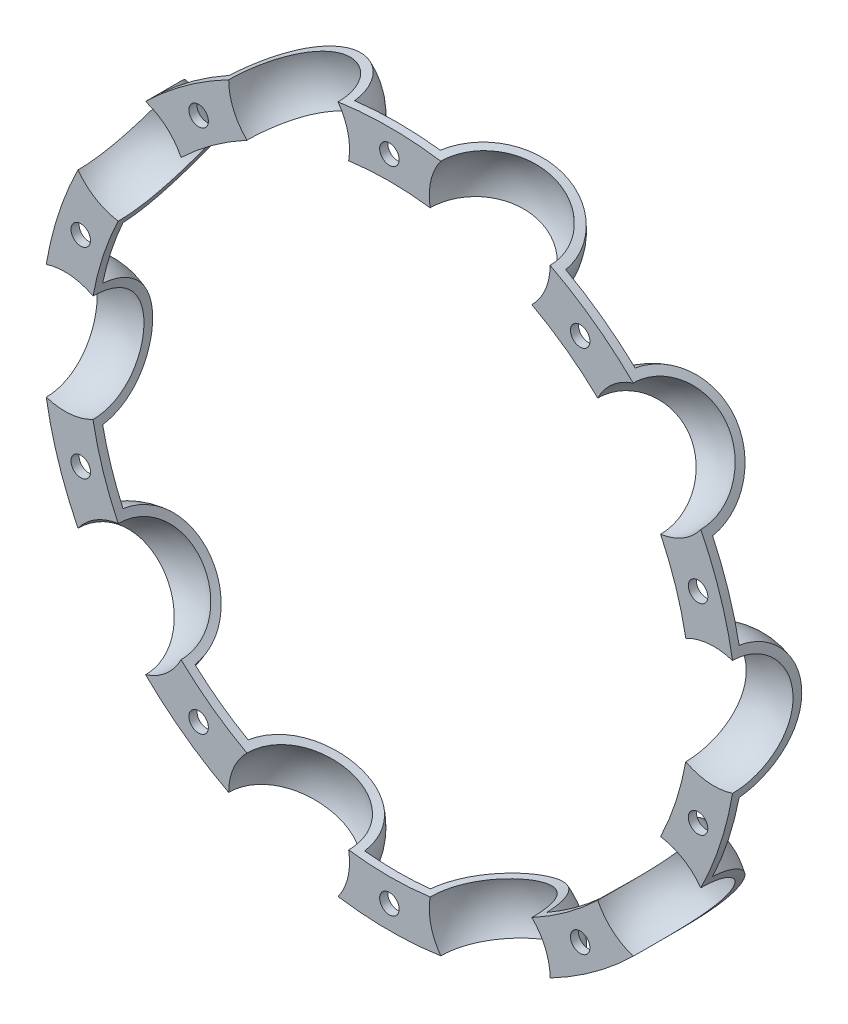
SolidWorks part; units mm, degrees
ref_plane "Front Plane" through (0, 0, 0) normal (0, 0, 1) x (1, 0, 0)
ref_plane "Top Plane" through (0, 0, 0) normal (0, 1, 0) x (1, 0, 0)
ref_plane "Right Plane" through (0, 0, 0) normal (1, 0, 0) x (0, 0, -1)
sketch "Sketch1" plane through (0, 0, 0) normal (0, 0, 1) x (1, 0, 0)
  circle A0 centre (0, 0) radius 10.71
  circle A1 centre (0, 0) radius 9.27
  dimension "D1" = 21.42
  dimension "D2" = 18.54
extrude "Boss-Extrude1" add sketch "Sketch1" along normal mid plane 2.11
sketch "Sketch2" plane through (0, 0, 1.055) normal (0, 0, 1) x (1, 0, 0)
  line L0 (8.13, 0) -> (11.85, 0) construction
  line L1 (8.13, 0) -> (11.85, 0)
  line L2 (9.27, 0) -> (10.71, 0) construction
  arc A0 (11.85, 0) -> (8.13, 0) centre (9.99, 0) ccw
  circle A1 centre (0, 0) radius 9.27 construction
  circle A2 centre (0, 0) radius 10.71 construction
  point P12 (9.99, 0)
  dimension "D1" = 3.72
revolve "Cut-Revolve1" cut sketch "Sketch2" angle 360 about L0
pattern_circular "CirPattern1" count 10 over 360 about axis through (0, 0, 0) along (0, 0, 1) of "Cut-Revolve1"
shell "Shell2" thickness 0.25
sketch "Sketch3" plane through (0, 0, 0.805) normal (0, 0, -1) x (-1, 0, 0)
  line L0 (0, 10.71) -> (0, 9.27) construction
  arc A0 (1.321, 10.6282) -> (-1.321, 10.6282) centre (0, 0) ccw construction
  arc A1 (1.0116, 9.2146) -> (-1.0116, 9.2146) centre (0, 0) ccw construction
  circle A2 centre (0, 9.99) radius 0.3
  dimension "D1" = 0.6
extrude "Cut-Extrude1" cut sketch "Sketch3" against normal through all
pattern_circular "CirPattern2" count 10 over 360 about axis through (0, 0, 0) along (0, 0, 1) of "Cut-Extrude1"
